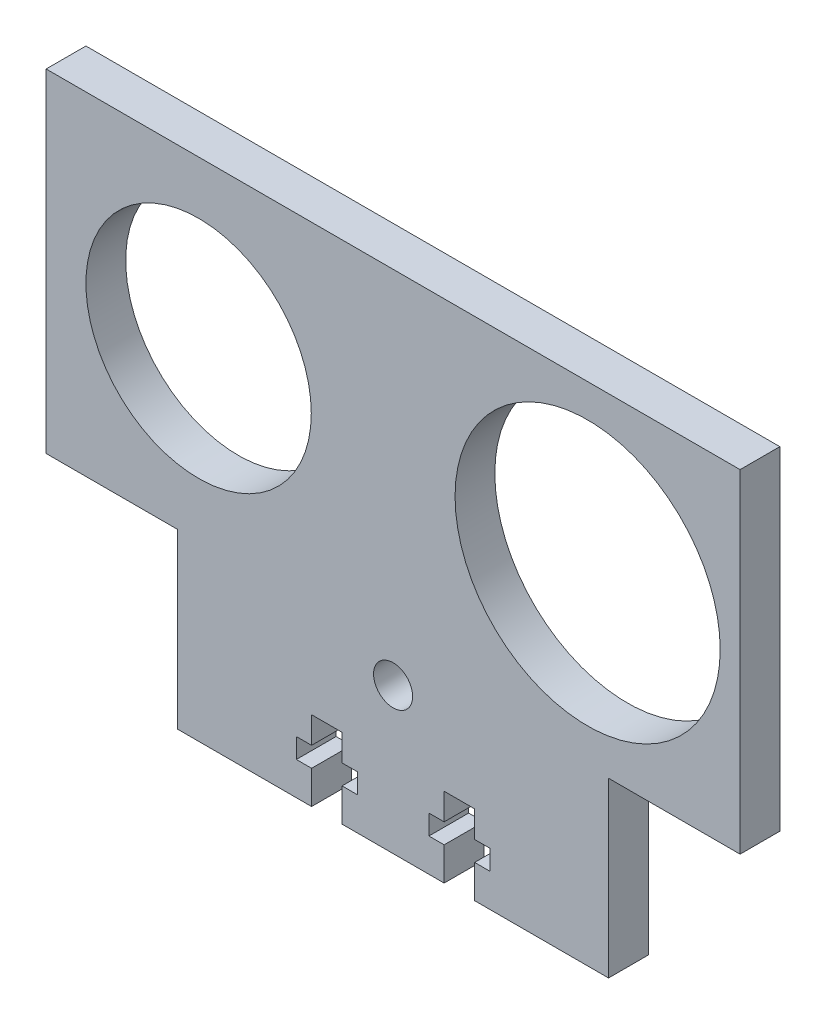
SolidWorks part; units mm, degrees
material "ABS"
ref_plane "Front Plane" through (0, 0, 0) normal (0, 0, 1) x (1, 0, 0)
ref_plane "Top Plane" through (0, 0, 0) normal (0, 1, 0) x (1, 0, 0)
ref_plane "Right Plane" through (0, 0, 0) normal (1, 0, 0) x (0, 0, -1)
sketch "Sketch1" plane through (0, 0, 0) normal (0, 0, 1) x (1, 0, 0)
  line L0 (0, 0) -> (-29.3449, 29.3449) construction
  line L1 (0, 0) -> (0, 54.3449) construction
  line L2 (-32.5, 4.1) -> (-32.5, -22)
  line L3 (-32.5, -22) -> (32.5, -22)
  line L4 (32.5, 4.1) -> (52.3449, 4.1)
  line L5 (0, 0) -> (0, -22) construction
  line L6 (52.3449, 4.1) -> (52.3449, 54.3449)
  line L7 (0, 0) -> (29.3449, 29.3449) construction
  line L10 (-32.5, 4.1) -> (-52.3449, 4.1)
  line L11 (-52.3449, 4.1) -> (-52.3449, 54.3449)
  line L12 (-52.3449, 54.3449) -> (52.3449, 54.3449)
  line L13 (32.5, 4.1) -> (32.5, -22)
  circle A0 centre (0, 0) radius 2.95
  circle A1 centre (-29.3449, 29.3449) radius 17
  circle A2 centre (29.3449, 29.3449) radius 20
  point P16 (0, 54.3449)
  dimension "D1" = 5.9
  dimension "D9" = 34
  dimension "D10" = 40
  dimension "D2" = 41.5
  dimension "D4" = 45
  dimension "D5" = 22
  dimension "D6" = 65
  dimension "D7" = 26.1
  dimension "D8" = 23
  dimension "D3" = 25
  dimension "D11" = 45
extrude "Boss-Extrude1" add sketch "Sketch1" along normal blind 6
sketch "Sketch3" plane through (0, 0, 6) normal (0, 0, 1) x (1, 0, 0)
  line L0 (-32.5, -22) -> (32.5, -22) construction
  line L1 (-12.3, -22) -> (-7.7, -22)
  line L2 (-12.3, -22) -> (-12.3, -17)
  line L3 (-12.3, -10) -> (-7.7, -10)
  line L4 (-7.7, -22) -> (-7.7, -17)
  line L5 (0, 0) -> (0, -22) construction
  line L6 (-7.7, -14) -> (-5.4, -14)
  line L7 (-14.6, -14) -> (-12.3, -14)
  line L8 (-14.6, -14) -> (-14.6, -17)
  line L9 (-14.6, -17) -> (-12.3, -17)
  line L10 (-5.4, -14) -> (-5.4, -17)
  line L11 (-12.3, -14) -> (-12.3, -10)
  line L12 (-7.7, -17) -> (-5.4, -17)
  line L13 (-7.7, -14) -> (-7.7, -10)
  line L14 (7.7, -14) -> (7.7, -10)
  line L15 (7.7, -17) -> (5.4, -17)
  line L16 (12.3, -14) -> (12.3, -10)
  line L17 (5.4, -14) -> (5.4, -17)
  line L18 (14.6, -17) -> (12.3, -17)
  line L19 (14.6, -14) -> (14.6, -17)
  line L20 (14.6, -14) -> (12.3, -14)
  line L21 (7.7, -14) -> (5.4, -14)
  line L22 (7.7, -22) -> (7.7, -17)
  line L23 (12.3, -10) -> (7.7, -10)
  line L24 (12.3, -22) -> (12.3, -17)
  line L25 (12.3, -22) -> (7.7, -22)
  point P6 (-10, -10)
  point P18 (-13.45, -17)
  dimension "D1" = 4.6
  dimension "D2" = 10
  dimension "D3" = 12
  dimension "D4" = 9.2
  dimension "D5" = 3
  dimension "D6" = 5
extrude "Cut-Extrude2" cut sketch "Sketch3" against normal through all
equation "\"smallPulleyTeeth\"= 15"
equation "\"largePulleyTeeth\"= 30"
equation "\"eighthThick\"= 2.9mm"
equation "\"sixteenthThick\"= 1.7mm"
equation "\"quarterThick\"=6.0mm"
equation "\"OD\"= 145mm"
equation "\"puckAngle\"= 60.5deg"
equation "\"puckDiam\"= 76.5mm"
equation "\"axlePress\"= 5.9mm"
equation "\"D1@Sketch1\"=\"axlePress\""
equation "\"D1@Boss-Extrude1\"=\"quarterThick\""
equation "\"press\"= 0.2mm"
equation "\"wheelClear\"= 0.3mm"
equation "\"10-32clear\"= 4.8mm"
equation "\"D1@Sketch3\"=\"10-32clear\" - \"press\""
equation "\"6-32clear\"= 3.3mm"
equation "\"8-32clear\"= 4.0mm"
equation "\"wheelHeight\"= 22mm"
equation "\"D5@Sketch1\"=\"wheelHeight\""
equation "\"D7@Sketch1\"=\"eighthThick\"*9"
equation "\"4-40clear\"= 3.0mm"
equation "\"wheelWell\"= 65mm"
equation "\"D6@Sketch1\"=\"wheelWell\""
